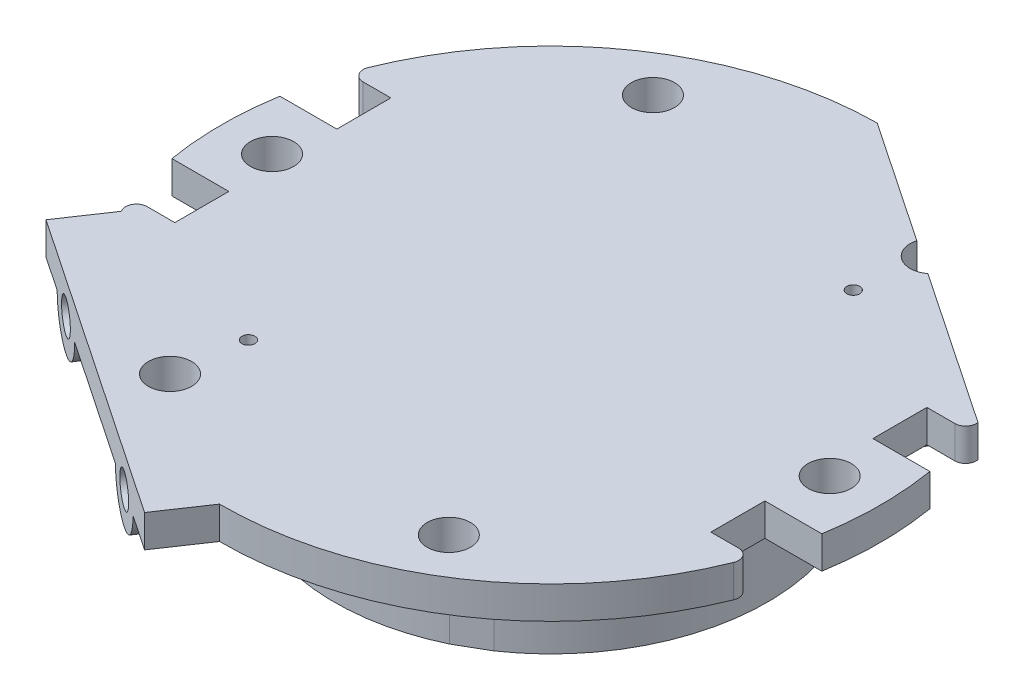
SolidWorks part; units mm, degrees
ref_plane "Alzado" through (0, 0, 0) normal (0, 0, 1) x (1, 0, 0)
ref_plane "Planta" through (0, 0, 0) normal (0, 1, 0) x (1, 0, 0)
ref_plane "Vista lateral" through (0, 0, 0) normal (1, 0, 0) x (0, 0, -1)
sketch "Croquis1" plane through (0, 0, 0) normal (0, 1, 0) x (1, 0, 0)
  circle A0 centre (0, 0) radius 30.5
extrude "Saliente-Extruir1" add sketch "Croquis1" along normal blind 3
sketch "Croquis5" plane through (0, 3, 0) normal (0, 1, 0) x (1, 0, 0)
  line L1 (28.8141, -5) -> (30.0874, -5)
  line L2 (28.8141, 5) -> (30.0874, 5)
  line L3 (-24.8141, 10) -> (-28.8141, 10)
  line L4 (24.8141, -5) -> (24.8141, -10)
  line L5 (-24.8141, -10) -> (-28.8141, -10)
  line L6 (24.8141, -5) -> (28.8141, -5)
  line L7 (24.8141, 5) -> (24.8141, 10)
  line L8 (-24.8141, 5) -> (-28.8141, 5)
  line L9 (-24.8141, 5) -> (-24.8141, 10)
  line L10 (-24.8141, -5) -> (-28.8141, -5)
  line L11 (-24.8141, -5) -> (-24.8141, -10)
  line L12 (24.8141, 5) -> (28.8141, 5)
  line L13 (24.8141, -10) -> (28.8141, -10)
  line L14 (24.8141, 10) -> (28.8141, 10)
  line L15 (-28.8141, 5) -> (-30.0874, 5)
  line L16 (-28.8141, -5) -> (-30.0874, -5)
  line L18 (-24.8141, 0) -> (-12.407, -21.4896)
  line L19 (-12.407, -21.4896) -> (12.407, -21.4896)
  line L20 (12.407, -21.4896) -> (24.8141, 0)
  line L21 (24.8141, 0) -> (12.407, 21.4896)
  line L22 (12.407, 21.4896) -> (-12.407, 21.4896)
  line L23 (-12.407, 21.4896) -> (-24.8141, 0)
  circle A0 centre (0, 0) radius 21.4896 construction
  circle A1 centre (0, 0) radius 30.5 construction
  arc A2 (-28.8141, 10) -> (-30.0874, 5) centre (0, 0) ccw
  arc A4 (-30.0874, -5) -> (-28.8141, -10) centre (0, 0) ccw
  arc A5 (30.0874, -5) -> (28.8141, -10) centre (0, 0) cw
  arc A6 (28.8141, 10) -> (30.0874, 5) centre (0, 0) cw
  circle M2 centre (0, 0) radius 30.5
extrude "Cortar-Extruir3" cut sketch "Croquis5" against normal blind 4 contours L10 L16 L5 L11 M2 | L15 L8 L9 L3 M2 | L14 L7 L12 L2 M2 | L4 L13 L1 L6 M2 region at (27.1844, 3, 7.3876) region at (-27.1844, 3, 7.3876) region at (27.1844, 3, -7.3876) region at (-27.1844, 3, -7.3876)
sketch "Croquis7" plane through (0, 3, 0) normal (0, 1, 0) x (1, 0, 0)
  line L2 (25.8141, 0) -> (12.907, 22.3556)
  line L3 (12.907, 22.3556) -> (-12.907, 22.3556)
  line L4 (-12.907, 22.3556) -> (-25.8141, 0)
  line L5 (-25.8141, 0) -> (-12.907, -22.3556)
  line L6 (-12.907, -22.3556) -> (12.907, -22.3556)
  line L7 (12.907, -22.3556) -> (25.8141, 0)
  circle A0 centre (25.8141, 0) radius 2
  circle A4 centre (-25.8141, 0) radius 2
  circle A5 centre (0, 0) radius 22.3556 construction
  circle A6 centre (12.907, 22.3556) radius 2
  circle A7 centre (-12.907, -22.3556) radius 2
  circle A8 centre (-12.907, 22.3556) radius 2
  circle A9 centre (12.907, -22.3556) radius 2
extrude "Cortar-Extruir4" cut sketch "Croquis7" against normal blind 10 contours A8 L4 L3 | A4 L4 L5 | A4 L5 L4 | A8 L3 L4 | L2 A6 L3 | L3 A6 L2 | L7 A0 L2 | L2 A0 L7 | A7 L5 L6 | A7 L6 L5 | L6 A9 L7 | L7 A9 L6 | A4 region at (24.7114, 3, 0) region at (26.3654, 3, 0) region at (12.3557, 3, -21.4007) region at (13.1827, 3, -22.8331) region at (13.1827, 3, 22.8331) region at (12.3557, 3, 21.4007) region at (-12.3557, 3, -21.4007) region at (-13.1827, 3, -22.8331) region at (-13.1827, 3, 22.8331) region at (-12.3557, 3, 21.4007) region at (-24.7114, 3, 0) region at (-26.3654, 3, 0)
sketch "Croquis8" plane through (0, 3, 0) normal (0, 1, 0) x (1, 0, 0)
  line L0 (0, 0) -> (12, 0)
  line L1 (12, 0) -> (12, 16)
  line L2 (0, 0) -> (-12, 0)
  line L3 (-12, 0) -> (-12, -16)
  circle A0 centre (12, 16) radius 0.6
  circle A1 centre (-12, -16) radius 0.6
extrude "Cortar-Extruir5" cut sketch "Croquis8" against normal blind 3 contours A1 | A0 region at (11.5877, 3, -16.4123) region at (-11.5877, 3, 15.5877)
sketch "Croquis9" plane through (0, 3, 0) normal (0, 1, 0) x (1, 0, 0)
  line L2 (-10, 17.3205) -> (-8.701, 18.0705)
  line L5 (25.6318, 16.5306) -> (27.1318, 13.9325)
  line L6 (-10, 17.3205) -> (-11.299, 16.5705)
  line L8 (10, -17.3205) -> (8.701, -18.0705)
  line L9 (10, -17.3205) -> (11.299, -16.5705)
  circle A0 centre (0, 0) radius 20.0562
  circle A1 centre (-12, -16) radius 3
  circle A2 centre (12, 16) radius 3
extrude "Saliente-Extruir2" add sketch "Croquis9" against normal blind 13 contours L2 L6 | L8 L9 region at (0, 3, 0)
sketch "Croquis11" plane through (14.0495, 0, -20.8293) normal (0.5592, 0, -0.829) x (-0.829, 0, -0.5592)
  line L1 (17.2916, 0) -> (-17.2916, 0)
  line L2 (17.2916, 0) -> (17.2916, 3)
  line L3 (17.2916, 3) -> (-17.2916, 3)
  line L4 (-17.2916, 0) -> (-17.2916, 3)
extrude "Saliente-Extruir3" add sketch "Croquis11" along normal blind 6
sketch "Croquis12" plane through (0, 3, 0) normal (0, 1, 0) x (1, 0, 0)
  circle A0 centre (12.907, 22.3556) radius 2
extrude "Cortar-Extruir7" cut sketch "Croquis12" against normal blind 3
sketch "Croquis13" plane through (17.4047, 0, -25.8035) normal (0.5592, 0, -0.829) x (-0.829, 0, -0.5592)
  line L0 (-17.2916, 0) -> (17.2916, 0)
  line L1 (17.2916, 3) -> (-17.2916, 3)
  line L2 (17.2916, 3) -> (-17.2916, 3) construction
  line L3 (17.2916, 0) -> (17.2916, 3) construction
  circle A1 centre (10, 0) radius 3
  circle A2 centre (-10, 0) radius 3
  circle A3 centre (10, 0) radius 1.5
  circle A5 centre (-10, 0) radius 1.5
  line M4 (-17.2916, 0) -> (17.2916, 0)
extrude "Saliente-Extruir4" add sketch "Croquis13" against normal blind 20 contours A3 L0 A1 | A3 L0 A1 | A5 L0 A2 | A5 L0 A2 | A5 M4 | A3 M4 region at (25.6951, 1.5671, -20.2116) region at (25.6951, -0.6366, -20.2116) region at (23.8297, -0.0671, -21.4698) region at (10.8337, 2.0739, -30.2358) region at (10.9797, -0.0671, -30.1373) region at (9.1143, -0.6366, -31.3955)
sketch "Croquis14" plane through (17.4047, 0, -25.8035) normal (0.5592, 0, -0.829) x (-0.829, 0, -0.5592)
  circle A0 centre (-10, 0) radius 1.5
  circle A1 centre (10, 0) radius 1.5
extrude "Cortar-Extruir8" cut sketch "Croquis14" against normal blind 6
sketch "Croquis15" plane through (0, 3, 0) normal (0, 1, 0) x (1, 0, 0)
  line L0 (28.3849, 11.16) -> (-0.2859, 30.4987)
  line L1 (28.3849, 11.16) -> (0.1409, -30.7136)
  line L2 (-0.2859, 30.4987) -> (-28.5299, -11.3749)
  line L3 (0.1409, -30.7136) -> (-28.5299, -11.3749)
  circle A0 centre (-0.2859, 0) radius 30.7165
  arc M12 (-28.8141, -10) -> (28.8141, -10) centre (0, 0) ccw
  circle M28 centre (-12.907, -22.3556) radius 2
extrude "Cortar-Extruir9" cut sketch "Croquis15" against normal blind 3 contours L3 M12 M28 region at (-15.494, 3, 22.7434)
sketch "Croquis16" plane through (-14.1945, 0, 21.0442) normal (-0.5592, 0, 0.829) x (0.829, 0, 0.5592)
  line L0 (-16.9088, 0) -> (-16.9088, 3)
  line L1 (-16.9088, 0) -> (16.78, 0)
  line L2 (-16.9088, 3) -> (16.78, 3)
  line L3 (16.78, 0) -> (16.78, 3)
extrude "Saliente-Extruir5" add sketch "Croquis16" along normal blind 6
sketch "Croquis17" plane through (0, 3, 0) normal (0, 1, 0) x (1, 0, 0)
  circle A0 centre (-12.907, -22.3556) radius 2
extrude "Cortar-Extruir10" cut sketch "Croquis17" against normal blind 3
sketch "Croquis18" plane through (-17.5497, 0, 26.0185) normal (-0.5592, 0, 0.829) x (0.829, 0, 0.5592)
  line L2 (-16.9088, 0) -> (16.78, 0) construction
  circle A0 centre (9.9356, 0) radius 3
  circle A1 centre (-10.0644, 0) radius 3
extrude "Saliente-Extruir6" add sketch "Croquis18" against normal blind 25
sketch "Croquis19" plane through (-17.5497, 0, 26.0185) normal (-0.5592, 0, 0.829) x (0.829, 0, 0.5592)
  circle A0 centre (-10.0644, 0) radius 1.5
  circle A1 centre (9.9356, 0) radius 1.5
extrude "Cortar-Extruir11" cut sketch "Croquis19" against normal blind 5
sketch "Croquis20" plane through (17.4047, 0, -25.8035) normal (0.5592, 0, -0.829) x (-0.829, 0, -0.5592)
  line L0 (17.2916, 3) -> (17.2916, 0)
  line L1 (17.2916, 0) -> (13, 0)
  line L2 (-7, 0) -> (7, 0) construction
  line L3 (7, 0) -> (-7, 0)
  line L4 (-13, 0) -> (-17.2916, 0)
  line L5 (-17.2916, 0) -> (-17.2916, 3)
  line L6 (-17.2916, 3) -> (17.2916, 3)
  arc A0 (13, 0) -> (7, 0) centre (10, 0) cw
  arc A1 (7, 0) -> (13, 0) centre (10, 0) ccw construction
  arc A2 (-7, 0) -> (-13, 0) centre (-10, 0) cw
extrude "Cortar-Extruir12" cut sketch "Croquis20" against normal blind 6
sketch "Croquis21" plane through (-17.5497, 0, 26.0185) normal (-0.5592, 0, 0.829) x (0.829, 0, 0.5592)
  line L0 (-13.0644, 0) -> (-16.9088, 0)
  line L1 (-16.9088, 0) -> (-16.9088, 3)
  line L2 (-16.9088, 3) -> (16.78, 3)
  line L3 (16.78, 3) -> (16.78, 0)
  line L4 (16.78, 0) -> (12.9356, 0)
  line L5 (6.9356, 0) -> (-7.0644, 0)
  arc A0 (-13.0644, 0) -> (-7.0644, 0) centre (-10.0644, 0) ccw
  arc A1 (6.9356, 0) -> (12.9356, 0) centre (9.9356, 0) ccw
extrude "Cortar-Extruir13" cut sketch "Croquis21" against normal blind 6
sketch "Croquis22" plane through (-14.1945, 0, 21.0442) normal (-0.5592, 0, 0.829) x (0.829, 0, 0.5592)
  circle A0 centre (-10.0644, 0) radius 1.5
  circle A1 centre (9.9356, 0) radius 1.5
extrude "Cortar-Extruir14" cut sketch "Croquis22" against normal blind 6
sketch "Croquis23" plane through (14.0495, 0, -20.8293) normal (0.5592, 0, -0.829) x (-0.829, 0, -0.5592)
  circle A0 centre (-10, 0) radius 1.5
  circle A1 centre (10, 0) radius 1.5
extrude "Cortar-Extruir15" cut sketch "Croquis23" against normal blind 6
fillet "Redondeo1" radius 1 4 edges at (-28.8141, 1.5, -10) (-28.8141, 1.5, 10) (28.8141, 1.5, 10) (28.8141, 1.5, -10)
sketch "Croquis24" plane through (-14.1945, 0, 21.0442) normal (-0.5592, 0, 0.829) x (0.829, 0, 0.5592)
  line L0 (16.9088, 3) -> (16.9088, 0)
  line L1 (16.9088, 0) -> (12.9356, 0)
  line L2 (6.9356, 0) -> (-7.0644, 0)
  line L3 (-13.0644, 0) -> (-16.9088, 0)
  line L4 (-16.9088, 0) -> (-16.9088, 3)
  line L5 (-16.9088, 3) -> (16.9088, 3)
  arc A0 (6.9356, 0) -> (12.9356, 0) centre (9.9356, 0) ccw
  arc A1 (-13.0644, 0) -> (-7.0644, 0) centre (-10.0644, 0) ccw
  circle A2 centre (-10.0644, 0) radius 1.5
  circle A3 centre (9.9356, 0) radius 1.5
extrude "Saliente-Extruir7" add sketch "Croquis24" along normal blind 5
sketch "Croquis25" plane through (0, 3, 0) normal (0, 1, 0) x (1, 0, 0)
  circle A0 centre (-12.907, -22.3556) radius 2
extrude "Cortar-Extruir16" cut sketch "Croquis25" against normal blind 3
